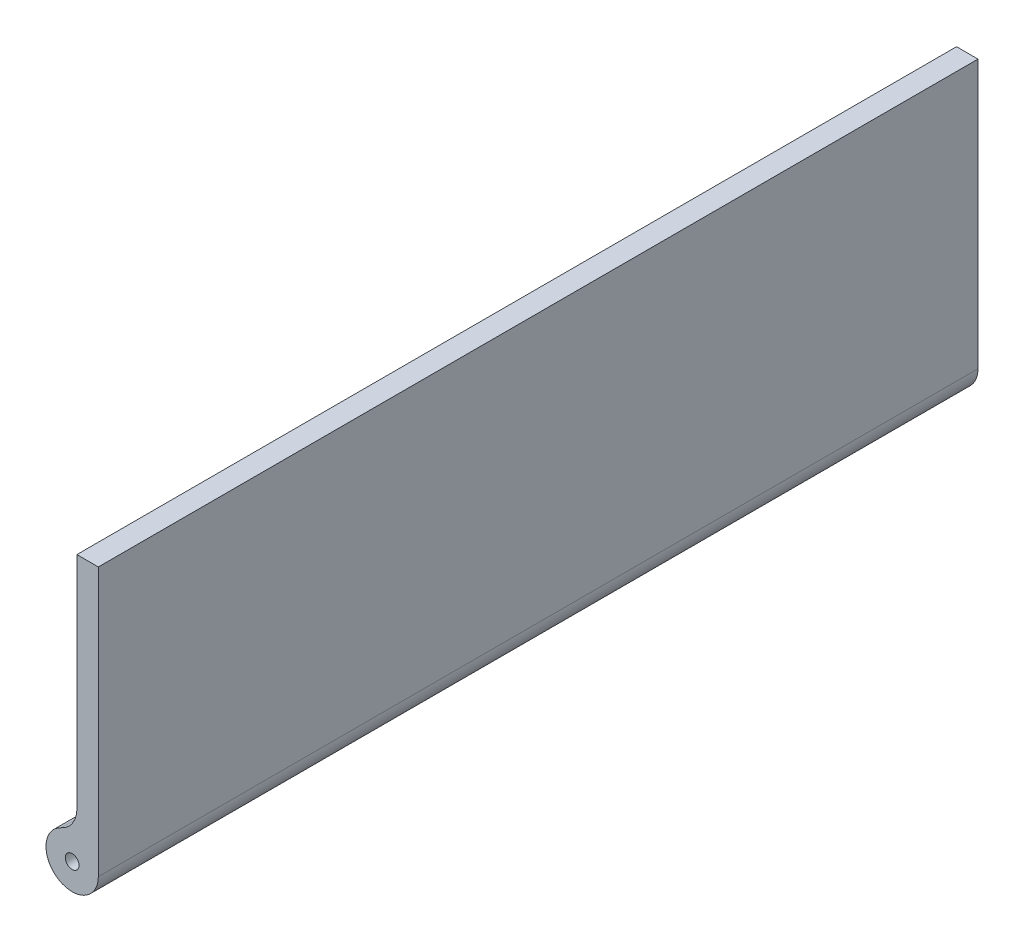
SolidWorks part; units mm, degrees
ref_plane "Front Plane" through (0, 0, 0) normal (0, 0, 1) x (1, 0, 0)
ref_plane "Top Plane" through (0, 0, 0) normal (0, 1, 0) x (1, 0, 0)
ref_plane "Right Plane" through (0, 0, 0) normal (1, 0, 0) x (0, 0, -1)
sketch "Sketch1" plane through (0, 0, 0) normal (0, 0, 1) x (1, 0, 0)
  line L0 (0, 0) -> (3.1723, 0) construction
  line L1 (2.44, 0) -> (2.44, 25)
  line L2 (0.44, 4.49) -> (0.44, 25)
  line L3 (0.44, 25) -> (2.44, 25)
  circle A0 centre (0, 0) radius 0.64
  arc A1 (-1.0175, 2.2177) -> (2.44, 0) centre (0, 0) ccw
  arc A2 (0.44, 4.49) -> (-1.0175, 2.2177) centre (-2.06, 4.49) cw
  point P3 (0, 0)
  dimension "D1" = 1.28
  dimension "D2" = 4.88
  dimension "D5" = 2.5
  dimension "D3" = 25
  dimension "D4" = 2
extrude "Boss-Extrude1" add sketch "Sketch1" along normal blind 82
